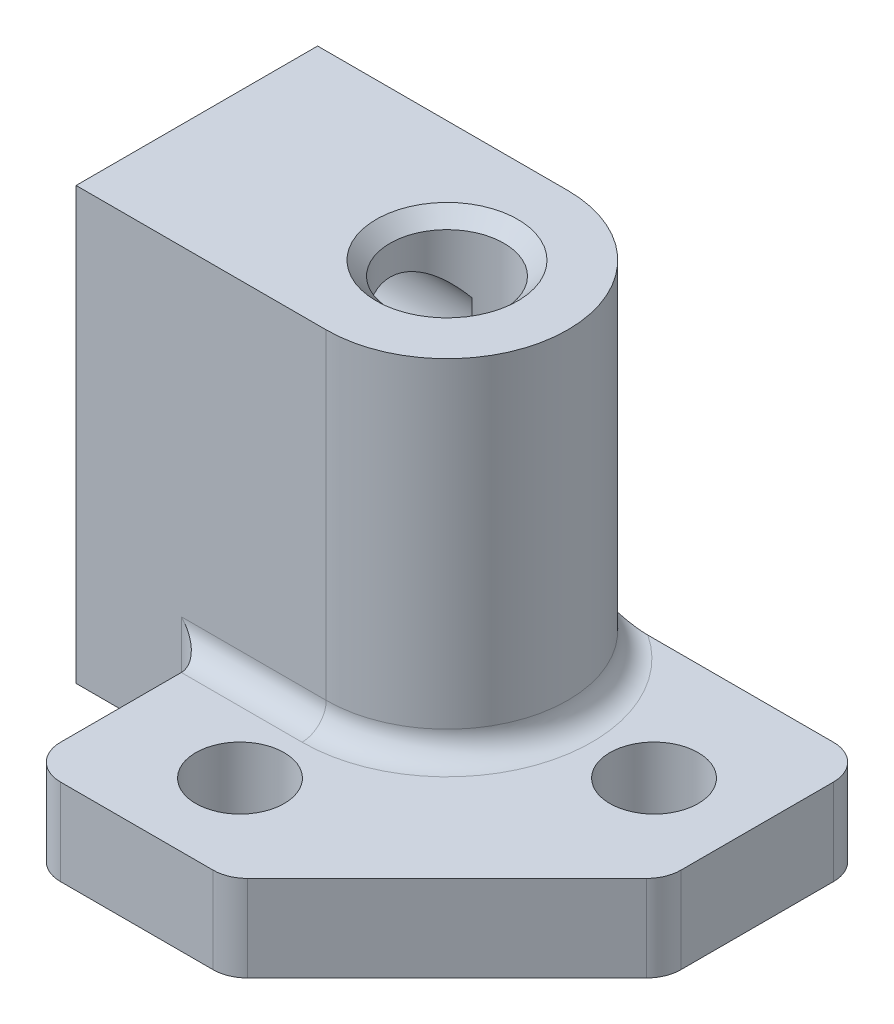
SolidWorks part; units mm, degrees
material "PLA2"
ref_plane "Front Plane" through (0, 0, 0) normal (0, 0, 1) x (1, 0, 0)
ref_plane "Top Plane" through (0, 0, 0) normal (0, 1, 0) x (1, 0, 0)
ref_plane "Right Plane" through (0, 0, 0) normal (1, 0, 0) x (0, 0, -1)
sketch "Sketch1" plane through (0, 0, 0) normal (0, 1, 0) x (1, 0, 0)
  circle A0 centre (0, 0) radius 2.0955
  circle A1 centre (0, 0) radius 4.445
  dimension "D1" = 4.191
  dimension "D2" = 8.89
extrude "Boss-Extrude1" add sketch "Sketch1" along normal blind 12.7
sketch "Sketch2" plane through (0, 0, 0) normal (0, -1, 0) x (1, 0, 0)
  line L0 (-4.445, 0) -> (-4.445, 11.049)
  line L1 (-4.445, 11.049) -> (2.9668, 11.049)
  line L8 (2.9668, 11.049) -> (11.049, 2.9668)
  line L9 (11.049, 2.9668) -> (11.049, -4.445)
  line L10 (0, 0) -> (0, 7.62) construction
  line L11 (11.049, -4.445) -> (0, -4.445)
  line L12 (0, 0) -> (7.62, 0) construction
  circle A5 centre (0, 0) radius 4.445 construction
  arc A6 (-4.445, 0) -> (0, -4.445) centre (0, 0) ccw
  circle A7 centre (0, 7.62) radius 1.6256
  circle A8 centre (7.62, 0) radius 1.6256
  point P12 (0, 12.065)
  dimension "D1" = 3.2512
  dimension "D2" = 7.62
  dimension "D3" = 7.62
  dimension "D4" = 11.049
  dimension "D5" = 11.049
  dimension "D6" = 11.43
extrude "Boss-Extrude2" add sketch "Sketch2" along normal blind 3.175
sketch "Sketch4" plane through (0, 12.7, 0) normal (0, 1, 0) x (1, 0, 0)
  line L0 (0, 4.445) -> (-9.2075, 4.445)
  line L1 (-9.2075, 4.445) -> (-9.2075, -4.445)
  line L2 (-9.2075, -4.445) -> (0, -4.445)
  line L3 (-9.2075, 0) -> (-2.0955, 0) construction
  circle A1 centre (0, 0) radius 4.445 construction
  circle A2 centre (0, 0) radius 2.0955 construction
  circle A3 centre (0, 0) radius 2.0955 construction
  arc A4 (0, 4.445) -> (0, -4.445) centre (0, 0) ccw
  dimension "D1" = 7.112
fillet "Fillet5" radius 1.27 4 edges at (-4.445, -1.5875, 11.049) (2.9668, -1.5875, 11.049) (11.049, -1.5875, 2.9668) (11.049, -1.5875, -4.445)
extrude "Boss-Extrude3" add sketch "Sketch4" against normal up to surface (15.875 mm away) up to face at (0, -3.175, 5.9944)
chamfer "Chamfer1" distance 0.508 angle 45 1 edges at (0, 12.7, 2.0955)
sketch "Sketch3" plane through (-9.2075, 0, 0) normal (1, 0, 0) x (0, 0, -1)
  line L0 (0, 0) -> (0, 12.7) construction
  line L1 (2.0955, 12.7) -> (-2.0955, 12.7) construction
  line L2 (4.445, 12.7) -> (-4.445, 12.7) construction
  circle A0 centre (0, 8.89) radius 2.2225
  circle A1 centre (0, 2.54) radius 2.2225
  dimension "D1" = 4.445
  dimension "0.2" = 6.35
  dimension "D3" = 3.81
extrude "Cut-Extrude1" cut sketch "Sketch3" along normal blind 8.255
fillet "Fillet6" radius 0.889 3 edges at (-2.2225, 0, 4.445) (4.445, 0, 0) (-4.445, -1.5875, 4.445)
